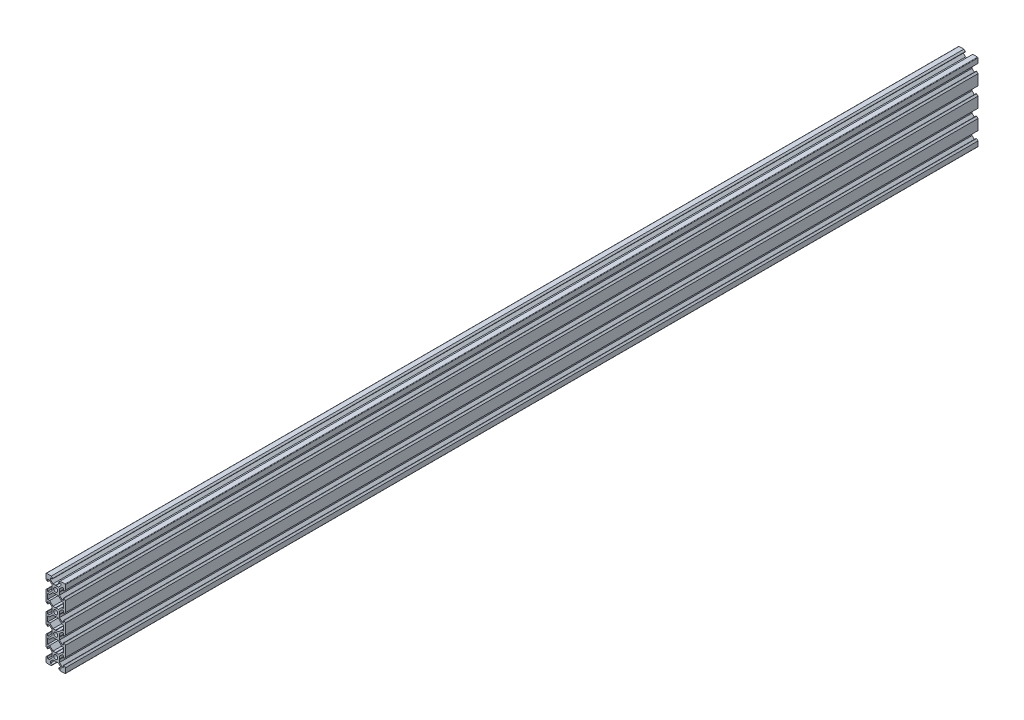
SolidWorks part; units mm, degrees
ref_plane "Plan de face" through (0, 0, 0) normal (0, 0, 1) x (1, 0, 0)
ref_plane "Plan de dessus" through (0, 0, 0) normal (0, 1, 0) x (1, 0, 0)
ref_plane "Plan de droite" through (0, 0, 0) normal (1, 0, 0) x (0, 0, -1)
ref_axis "Axe" through (0, 0, -13.782) along (0, 0, 1)
sketch "Esquisse1" plane through (0, 0, 0) normal (0, 0, 1) x (1, 0, 0)
  line L0 (0, 27.6392) -> (0, -27.6392) construction
  line L1 (-33.6074, 0) -> (33.6074, 0) construction
  line L2 (0, 0) -> (-22.2114, 22.2114) construction
  line L3 (-9.5, 10) -> (-4.58, 10)
  line L4 (-4.58, 10) -> (-3.125, 8.545)
  line L5 (-3.125, 8.545) -> (-3.125, 8.2)
  line L6 (-3.125, 8.2) -> (-5.5, 8.2)
  line L7 (-2.8393, 3.9) -> (-5.5, 6.5607)
  line L8 (-2.8393, 3.9) -> (-0.21, 3.9)
  line L9 (-5.5, 6.5607) -> (-5.5, 8.2)
  line L10 (0, 3.69) -> (0, 2.1)
  line L11 (-3.9, 2.8393) -> (-6.5607, 5.5)
  line L12 (-8.545, 3.125) -> (-8.2, 3.125)
  line L13 (-8.2, 3.125) -> (-8.2, 5.5)
  line L14 (-6.5607, 5.5) -> (-8.2, 5.5)
  line L15 (-10, 4.58) -> (-8.545, 3.125)
  line L16 (-10, 9.5) -> (-10, 4.58)
  line L17 (-0.21, 3.9) -> (0, 3.69)
  line L18 (-3.9, 2.8393) -> (-3.9, 0.21)
  line L19 (-6.2393, -12.7) -> (-8.2, -12.7)
  line L20 (-3.9, 0.21) -> (-3.69, 0)
  line L21 (-0.21, -3.9) -> (0, -3.69)
  line L22 (0, -3.69) -> (0, -2.1)
  line L23 (-6.5607, -5.5) -> (-8.2, -5.5)
  line L24 (-2.8393, -3.9) -> (-0.21, -3.9)
  line L25 (-8.545, -3.125) -> (-8.2, -3.125)
  line L26 (-10, -4.58) -> (-8.545, -3.125)
  line L27 (-8.2, -3.125) -> (-8.2, -5.5)
  line L28 (-2.8393, -3.9) -> (-6.2393, -7.3)
  line L29 (-3.9, -2.8393) -> (-6.5607, -5.5)
  line L30 (-3.9, -2.8393) -> (-3.9, -0.21)
  line L31 (-3.9, -0.21) -> (-3.69, 0)
  line L32 (-6.2393, -7.3) -> (-8.2, -7.3)
  line L33 (-8.2, -7.3) -> (-8.2, -12.7)
  line L34 (-8.2, -10) -> (-10, -10) construction
  line L35 (-10, -15.42) -> (-10, -4.58)
  line L36 (-3.9, -19.79) -> (-3.69, -20)
  line L37 (-3.9, -17.1607) -> (-3.9, -19.79)
  line L38 (-3.9, -17.1607) -> (-6.5607, -14.5)
  line L39 (-2.8393, -16.1) -> (-6.2393, -12.7)
  line L40 (-8.2, -16.875) -> (-8.2, -14.5)
  line L41 (-10, -15.42) -> (-8.545, -16.875)
  line L42 (-8.545, -16.875) -> (-8.2, -16.875)
  line L43 (-2.8393, -16.1) -> (-0.21, -16.1)
  line L44 (-6.5607, -14.5) -> (-8.2, -14.5)
  line L45 (0, -16.31) -> (0, -17.9)
  line L46 (-0.21, -16.1) -> (0, -16.31)
  line L47 (-8.2, -30) -> (-10, -30) construction
  line L48 (-3.69, -20) -> (0, -20) construction
  line L49 (-0.21, -23.9) -> (0, -23.69)
  line L50 (0, -23.69) -> (0, -22.1)
  line L51 (-6.5607, -25.5) -> (-8.2, -25.5)
  line L52 (-2.8393, -23.9) -> (-0.21, -23.9)
  line L53 (-8.545, -23.125) -> (-8.2, -23.125)
  line L54 (-10, -24.58) -> (-8.545, -23.125)
  line L55 (-8.2, -23.125) -> (-8.2, -25.5)
  line L56 (-2.8393, -23.9) -> (-6.2393, -27.3)
  line L57 (-3.9, -22.8393) -> (-6.5607, -25.5)
  line L58 (-3.9, -22.8393) -> (-3.9, -20.21)
  line L59 (-3.9, -20.21) -> (-3.69, -20)
  line L60 (-10, -24.58) -> (-10, -35.42)
  line L61 (-8.2, -32.7) -> (-8.2, -27.3)
  line L62 (-3.69, -40) -> (0, -40) construction
  line L63 (-8.2, -50) -> (-10, -50) construction
  line L64 (0, -60) -> (-22.2114, -82.2114) construction
  line L65 (-33.6074, -60) -> (33.6074, -60) construction
  line L66 (0, -87.6392) -> (0, -32.3608) construction
  line L67 (-6.2393, -32.7) -> (-8.2, -32.7)
  line L68 (-3.9, -39.79) -> (-3.69, -40)
  line L69 (-3.9, -37.1607) -> (-3.9, -39.79)
  line L70 (-3.9, -37.1607) -> (-6.5607, -34.5)
  line L71 (-2.8393, -36.1) -> (-6.2393, -32.7)
  line L72 (-8.2, -36.875) -> (-8.2, -34.5)
  line L73 (-10, -35.42) -> (-8.545, -36.875)
  line L74 (-8.545, -36.875) -> (-8.2, -36.875)
  line L75 (-6.2393, -27.3) -> (-8.2, -27.3)
  line L76 (-2.8393, -36.1) -> (-0.21, -36.1)
  line L77 (-6.5607, -34.5) -> (-8.2, -34.5)
  line L78 (0, -36.31) -> (0, -37.9)
  line L79 (-0.21, -36.1) -> (0, -36.31)
  line L80 (-0.21, -43.9) -> (0, -43.69)
  line L81 (0, -43.69) -> (0, -42.1)
  line L82 (-6.5607, -45.5) -> (-8.2, -45.5)
  line L83 (-2.8393, -43.9) -> (-0.21, -43.9)
  line L84 (-8.545, -43.125) -> (-8.2, -43.125)
  line L85 (-10, -44.58) -> (-8.545, -43.125)
  line L86 (-8.2, -43.125) -> (-8.2, -45.5)
  line L87 (-2.8393, -43.9) -> (-6.2393, -47.3)
  line L88 (-3.9, -42.8393) -> (-6.5607, -45.5)
  line L89 (-3.9, -42.8393) -> (-3.9, -40.21)
  line L90 (-3.9, -40.21) -> (-3.69, -40)
  line L91 (-10, -44.58) -> (-10, -55.42)
  line L92 (-8.2, -52.7) -> (-8.2, -47.3)
  line L93 (-6.2393, -52.7) -> (-8.2, -52.7)
  line L94 (-3.9, -59.79) -> (-3.69, -60)
  line L95 (-3.9, -57.1607) -> (-3.9, -59.79)
  line L96 (-3.9, -57.1607) -> (-6.5607, -54.5)
  line L97 (-2.8393, -56.1) -> (-6.2393, -52.7)
  line L98 (-8.2, -56.875) -> (-8.2, -54.5)
  line L99 (-10, -55.42) -> (-8.545, -56.875)
  line L100 (-8.545, -56.875) -> (-8.2, -56.875)
  line L101 (-2.8393, -56.1) -> (-0.21, -56.1)
  line L102 (-6.5607, -54.5) -> (-8.2, -54.5)
  line L103 (0, -56.31) -> (0, -57.9)
  line L104 (-0.21, -56.1) -> (0, -56.31)
  line L105 (-3.9, -60.21) -> (-3.69, -60)
  line L106 (-6.2393, -47.3) -> (-8.2, -47.3)
  line L107 (-3.9, -62.8393) -> (-3.9, -60.21)
  line L108 (-0.21, -63.9) -> (0, -63.69)
  line L109 (-10, -69.5) -> (-10, -64.58)
  line L110 (-10, -64.58) -> (-8.545, -63.125)
  line L111 (-6.5607, -65.5) -> (-8.2, -65.5)
  line L112 (-8.2, -63.125) -> (-8.2, -65.5)
  line L113 (-8.545, -63.125) -> (-8.2, -63.125)
  line L114 (-3.9, -62.8393) -> (-6.5607, -65.5)
  line L115 (0, -63.69) -> (0, -62.1)
  line L116 (-5.5, -66.5607) -> (-5.5, -68.2)
  line L117 (-2.8393, -63.9) -> (-0.21, -63.9)
  line L118 (-2.8393, -63.9) -> (-5.5, -66.5607)
  line L119 (-3.125, -68.2) -> (-5.5, -68.2)
  line L120 (-3.125, -68.545) -> (-3.125, -68.2)
  line L121 (-4.58, -70) -> (-3.125, -68.545)
  line L122 (-9.5, -70) -> (-4.58, -70)
  arc A0 (0, -2.1) -> (0, 2.1) centre (0, 0) cw
  arc A1 (-9.5, 10) -> (-10, 9.5) centre (-9.5, 9.5) ccw
  arc A2 (0, -42.1) -> (0, -37.9) centre (0, -40) cw
  arc A3 (-9.5, -70) -> (-10, -69.5) centre (-9.5, -69.5) cw
  arc A4 (0, -17.9) -> (0, -22.1) centre (0, -20) ccw
  arc A5 (0, -57.9) -> (0, -62.1) centre (0, -60) ccw
  point P4 (0, 0)
  point P7 (0, 0)
  point P30 (-10, 10)
  point P60 (0, -20)
  point P146 (-10, -70)
  dimension "D5" = 11
  dimension "D2" = 2.1
  dimension "D3" = 6.25
  dimension "D10" = 0.5
  dimension "D4" = 9.16
  dimension "D6" = 1.5
  dimension "D7" = 1.8
  dimension "D8" = 4.3
  dimension "D9" = 20
  dimension "D11" = 0.42
  dimension "D12" = 10
  dimension "D13" = 1.8
extrude "Boss.-Extru.1" add sketch "Esquisse1" along normal blind 940
sketch "Esquisse3" plane through (0, 0, 940) normal (0, 0, 1) x (1, 0, 0)
  line L0 (0, 0) -> (-9.8536, 9.8536) construction
  line L1 (-8.2, 8.2) -> (-8.2, 6.57)
  line L2 (-8.2, 6.57) -> (-7.54, 6.57)
  line L3 (-7.54, 6.57) -> (-6.57, 7.54)
  line L4 (-8.2, 3.125) -> (-8.2, 5.5) construction
  line L5 (-6.57, 8.2) -> (-6.57, 7.54)
  line L6 (-8.2, 8.2) -> (-6.57, 8.2)
  line L7 (-5.5, 6.5607) -> (-5.5, 8.2) construction
  line L8 (-10, -30) -> (6.918, -30) construction
  line L9 (-10, -24.58) -> (-10, -35.42) construction
  line L10 (-8.2, -68.2) -> (-6.57, -68.2)
  line L11 (-6.57, -68.2) -> (-6.57, -67.54)
  line L12 (-7.54, -66.57) -> (-6.57, -67.54)
  line L13 (-8.2, -66.57) -> (-7.54, -66.57)
  line L14 (-8.2, -68.2) -> (-8.2, -66.57)
  arc A0 (-9.5, 10) -> (-10, 9.5) centre (-9.5, 9.5) ccw construction
  point P13 (-7.055, 7.055)
  point P14 (-6.57, 7.87)
  point P26 (-7.055, -67.055)
  dimension "D1" = 1.07
extrude "Enlèv. mat.-Extru.1" [suppressed] cut sketch "Esquisse3" against normal through all
mirror "Symétrie1" of "Enlèv. mat.-Extru.1", "Boss.-Extru.1"
